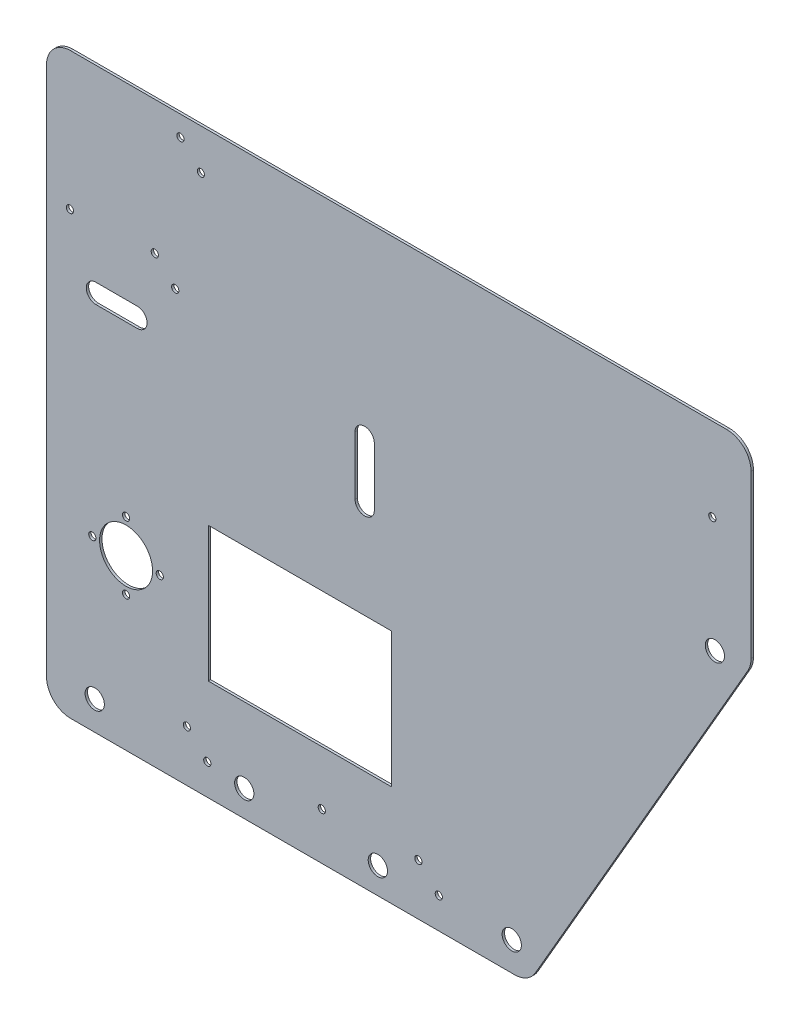
SolidWorks part; units mm, degrees
ref_plane "Front Plane" through (0, 0, 0) normal (0, 0, 1) x (1, 0, 0)
ref_plane "Top Plane" through (0, 0, 0) normal (0, 1, 0) x (1, 0, 0)
ref_plane "Right Plane" through (0, 0, 0) normal (1, 0, 0) x (0, 0, -1)
sketch "Sketch1" plane through (0, 0, 0) normal (0, 0, 1) x (1, 0, 0)
  line L0 (100, 80) -> (192.376, 80)
  line L1 (-100, -80) -> (100, -80)
  line L2 (-100, -80) -> (-100, 80)
  line L3 (-100, 80) -> (100, 80)
  line L4 (100, -80) -> (100, 80)
  line L5 (-100, -80) -> (100, 80) construction
  line L6 (-100, 80) -> (100, -80) construction
  line L7 (192.376, 80) -> (100, -80)
  line L8 (100, 80) -> (100, -80)
  line L10 (-100, 80) -> (192.376, 80)
  line L11 (-100, 80) -> (-100, 110)
  line L12 (-100, 110) -> (192.376, 110)
  line L13 (192.376, 80) -> (192.376, 110)
  point P0 (0, 0)
  dimension "D1" = 160
  dimension "D2" = 200
  dimension "D3" = 30
  dimension "D4" = 30
extrude "Boss-Extrude1" add sketch "Sketch1" along normal blind 1 contours L1 L4 L3 L2 | L7 L0 L4 | L11 L10 L13 L12 region at (0, 0, 0) region at (130.792, 26.6667, 0)
sketch "Sketch2" plane through (0, 0, 1) normal (0, 0, 1) x (1, 0, 0)
  line L0 (-100, -80) -> (100, -80) construction
  line L1 (192.376, 80) -> (100, -80) construction
  line L2 (-100, -80) -> (-100, 110) construction
  line L3 (-100, 110) -> (192.376, 110) construction
  line L4 (-79.5166, 78) -> (-62.3003, 78) construction
  line L7 (-100, -80) -> (-100, 110) construction
  line L8 (-29.8584, 15) -> (-29.8584, -35) construction
  line L9 (-79.5166, 82) -> (-62.3003, 82)
  line L10 (-79.5166, 74) -> (-62.3003, 74)
  line L11 (-32.8584, 18) -> (43.1416, 18)
  line L12 (-32.8584, 18) -> (-32.8584, -38)
  line L13 (-32.8584, -38) -> (43.1416, -38)
  line L14 (43.1416, 18) -> (43.1416, -38)
  line L15 (20.1416, 15) -> (-29.8584, 15) construction
  line L17 (40.1416, -35) -> (40.1416, 15) construction
  line L18 (32.0262, 82) -> (32.0262, 57.7776) construction
  line L19 (36.0262, 82) -> (36.0262, 57.7776)
  line L20 (28.0262, 82) -> (28.0262, 57.7776)
  circle A0 centre (93.0718, -68) radius 4
  circle A1 centre (177.3649, 78) radius 4
  circle A2 centre (-67, -10) radius 11
  circle A3 centre (-80, -68) radius 4
  circle A4 centre (-53, -10) radius 1.5
  circle A5 centre (-67, 4) radius 1.5
  circle A6 centre (-81, -10) radius 1.5
  circle A7 centre (-67, -24) radius 1.5
  circle A10 centre (32.0262, 70) radius 4 construction
  arc A11 (-79.5166, 82) -> (-79.5166, 74) centre (-79.5166, 78) ccw
  arc A12 (-62.3003, 74) -> (-62.3003, 82) centre (-62.3003, 78) ccw
  circle A32 centre (62.7961, -67.2426) radius 1.5
  circle A33 centre (54.3108, -58.7574) radius 1.5
  circle A34 centre (-33.2742, -67.2426) radius 1.5
  circle A35 centre (-41.7595, -58.7574) radius 1.5
  circle A36 centre (14.2259, -60.5) radius 1.5
  circle A37 centre (-46.589, 96.1388) radius 1.5
  circle A38 centre (-55.0743, 104.6241) radius 1.5
  circle A39 centre (-90.2956, 102.8814) radius 1.5
  circle A40 centre (176.3056, 125.4889) radius 1.5
  arc A41 (36.0262, 82) -> (28.0262, 82) centre (32.0262, 82) ccw
  arc A42 (28.0262, 57.7776) -> (36.0262, 57.7776) centre (32.0262, 57.7776) ccw
  circle A43 centre (-17.9479, -69.1174) radius 4
  circle A44 centre (37.4944, -69.1174) radius 4
  point P12 (-70.9085, 78)
  point P65 (32.0262, 69.8888)
  dimension "D3" = 8
  dimension "D4" = 8
  dimension "D9" = 22
  dimension "D10" = 8
  dimension "D12" = 3
  dimension "D13" = 3
  dimension "D14" = 3
  dimension "D15" = 3
  dimension "D16" = 14
  dimension "D20" = 4
  dimension "D22" = 8
  dimension "D23" = 3
  dimension "D24" = 20
  dimension "D25" = 3
  dimension "D1" = 12
  dimension "D2" = 12
  dimension "D5" = 32
  dimension "D6" = 12
  dimension "D7" = 33
  dimension "D8" = 70
  dimension "D11" = 12
  dimension "D17" = 14
  dimension "D18" = 14
  dimension "D19" = 14
  dimension "D21" = 40
  dimension "D26" = 3
  dimension "D27" = 3
  dimension "D28" = 8
  dimension "D29" = 3
extrude "Cut-Extrude1" cut sketch "Sketch2" against normal blind 3
sketch "Sketch3" plane through (0, 0, 1) normal (0, 0, 1) x (1, 0, 0)
  line L0 (192.376, 80) -> (192.376, 110) construction
  line L1 (-100, 110) -> (192.376, 110)
  line L2 (-100, 110) -> (-100, 160)
  line L3 (-100, 160) -> (192.376, 160)
  line L4 (192.376, 110) -> (192.376, 160)
  dimension "D1" = 50
extrude "Boss-Extrude2" add sketch "Sketch3" against normal blind 1
fillet "Fillet1" radius 10 5 edges at (100, -80, 0.5) (-100, -80, 0.5) (-100, 160, 0.5) (192.376, 160, 0.5) (192.376, 80, 0.5)
sketch "Sketch4" plane through (0, 0, 1) normal (0, 0, 1) x (1, 0, 0)
  circle A2 centre (-44.4423, 151.6241) radius 1.5
  circle A3 centre (-35.957, 143.1388) radius 1.5
  circle A4 centre (176.3056, 125.4889) radius 1.5
  dimension "D1" = 3
extrude "Cut-Extrude2" cut sketch "Sketch4" against normal blind 11
